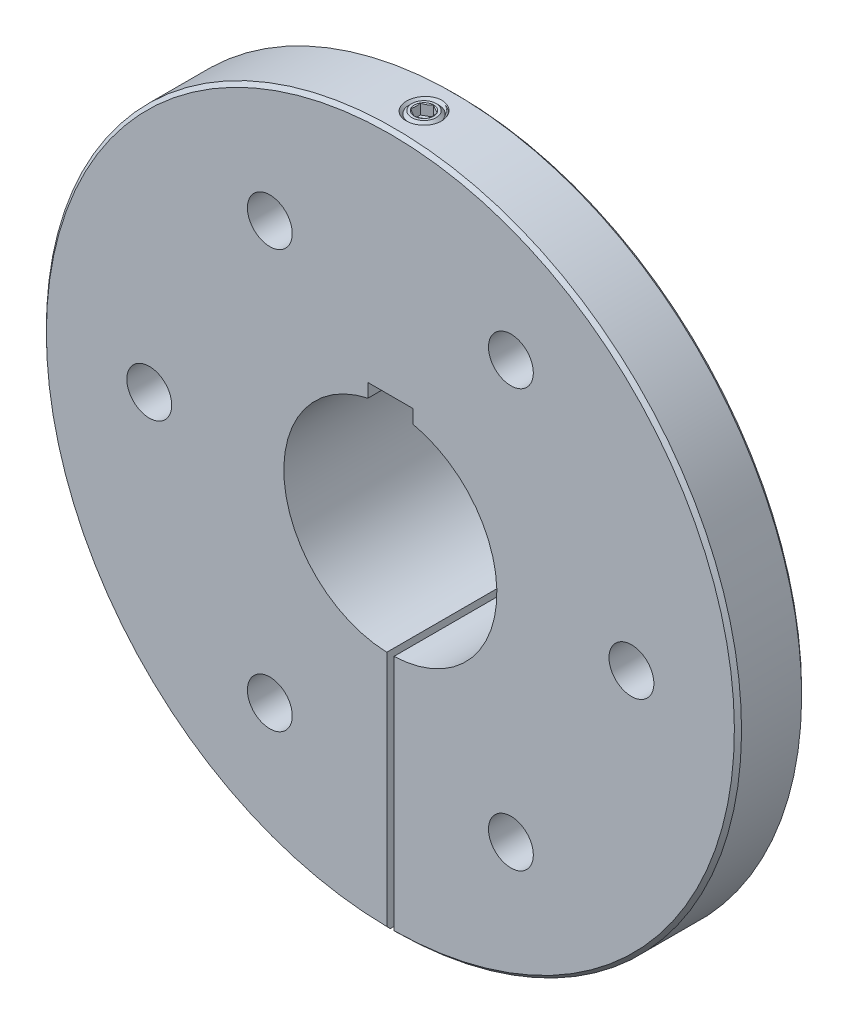
SolidWorks part; units mm, degrees
ref_plane "Front Plane" through (0, 0, 0) normal (0, 0, 1) x (1, 0, 0)
ref_plane "Top Plane" through (0, 0, 0) normal (0, 1, 0) x (1, 0, 0)
ref_plane "Right Plane" through (0, 0, 0) normal (1, 0, 0) x (0, 0, -1)
sketch "Sketch1" plane through (0, 0, 0) normal (1, 0, 0) x (0, 0, -1)
  line L0 (0, 0) -> (26.9875, 0) construction
  line L1 (0, 49.2125) -> (0, -49.2125) construction
  line L2 (12.7, 17.4625) -> (12.7, -17.4625) construction
  line L3 (9.525, 49.2125) -> (9.525, -49.2125) construction
  line L4 (12.7, 17.4625) -> (26.9875, 17.016) construction
  line L5 (26.9875, 17.016) -> (26.9875, -17.016) construction
  line L6 (26.9875, -17.016) -> (12.7, -17.4625)
  line L7 (26.9875, 17.016) -> (26.9875, 49.2125) construction
  line L8 (26.9875, 49.2125) -> (12.7, 49.2125) construction
  line L9 (12.7, 49.2125) -> (12.7, 17.4625) construction
  line L10 (0, 49.2125) -> (9.525, 49.2125) construction
  line L11 (9.525, 49.2125) -> (12.7, 49.2125) construction
  line L12 (0, -49.2125) -> (9.525, -49.2125) construction
  line L13 (26.9875, 0) -> (26.9875, -17.016) construction
  line L14 (26.9875, -15.0812) -> (0, -15.0813)
  line L15 (26.9875, -15.0812) -> (26.9875, -17.016)
  line L16 (0, -15.0813) -> (0, -48.7045)
  line L17 (12.7, -17.4625) -> (12.7, -16.6687)
  line L18 (12.7, -16.6687) -> (9.525, -16.6687)
  line L19 (9.525, -16.6687) -> (9.525, -48.7045)
  line L20 (0, -48.7045) -> (0.508, -49.2125)
  line L21 (0.508, -49.2125) -> (9.017, -49.2125)
  line L22 (9.017, -49.2125) -> (9.525, -48.7045)
  line L23 (26.9875, 17.4625) -> (26.9875, -17.4625) construction
  point P10 (9.525, 0)
  point P11 (12.7, 0)
  dimension "A" = 9.525
  dimension "B" = 34.925
  dimension "D" = 98.425
  dimension "E" = 17.4625
  dimension "F" = 14.2875
  dimension "G" = 3.175
  dimension "L" = 26.9875
  dimension "D2" = 3.175
  dimension "D3" = 0.7937
  dimension "D4" = 0.508
  dimension "Bore" = 30.1625
  dimension "D5" = 45
  dimension "D6" = 0.508
  dimension "D7" = 45
  dimension "Run" = 14.2875
  dimension "Rise" = 0.4465
revolve "Revolve1" add sketch "Sketch1" angle 360 mid plane about L0
sketch "Sketch2" plane through (0, 0, 0) normal (0, 0, 1) x (1, 0, 0)
  circle A0 centre (0, 0) radius 21.1455
  circle A1 centre (0, 0) radius 15.0813
  dimension "Bolt Circle" = 42.291
sketch "Sketch3" plane through (0, 0, 0) normal (0, 0, 1) x (1, 0, 0)
  line L1 (-0.508, 0) -> (0.508, 0)
  line L2 (-0.508, 0) -> (-0.508, -49.2125)
  line L3 (-0.508, -49.2125) -> (0.508, -49.2125)
  line L4 (0.508, 0) -> (0.508, -49.2125)
  dimension "D1" = 1.016
extrude "Cut-Extrude1" cut sketch "Sketch3" against normal through all
sketch "Sketch4" plane through (0, 0, 0) normal (0, 0, 1) x (1, 0, 0)
  line L0 (0, 0) -> (21.1455, 0) construction
  line L1 (0, 0) -> (-21.1455, 0) construction
  circle A0 centre (21.1455, 0) radius 2.413
  circle A1 centre (0, 0) radius 21.1455 construction
  circle A2 centre (-21.1455, 0) radius 2.413
  dimension "D1" = 42.291
  dimension "Cap Screw Size" = 4.826
sketch "Sketch16" plane through (0, 0, 0) normal (0, 0, 1) x (1, 0, 0)
  line L0 (0, 0) -> (0, 13.4938) construction
  line L1 (-3.175, 16.6687) -> (3.175, 16.6687)
  line L2 (-3.175, 16.6687) -> (-3.175, 13.4938)
  line L3 (-3.175, 13.4938) -> (3.175, 13.4938)
  line L4 (3.175, 16.6687) -> (3.175, 13.4938)
  line L5 (-3.175, 15.0813) -> (3.175, 15.0813) construction
  arc A0 (0.508, -15.0727) -> (-0.508, -15.0727) centre (0, 0) ccw construction
  dimension "Key Wd." = 6.35
  dimension "Key Dp." = 1.5875
extrude "Cut-Extrude7" cut sketch "Sketch16" against normal through all
ref_plane "Plane1" through (0, 49.2125, 0) normal (0, 1, 0) x (-1, 0, 0)
sketch "Sketch17" plane through (0, 49.2125, 0) normal (0, 1, 0) x (-1, 0, 0)
  line L0 (0, 0) -> (0, -9.525) construction
  line L1 (-3.175, 0) -> (3.175, 0) construction
  line L2 (-48.7045, -9.525) -> (48.7045, -9.525) construction
  circle A2 centre (0, -4.7625) radius 2.413
  point P1 (0, -2.3495)
  dimension "Set Screw Size" = 4.826
curve "Helix/Spiral3" pitch 1.0583 height 49.2125 turns 46.5 parameters "Pitch"=1.0583
sketch "Sketch18" plane through (0, 0, 0) normal (1, 0, 0) x (0, 0, -1)
  line L0 (3.1515, 50.2708) -> (3.1515, 49.2125) construction
  line L1 (3.1515, 49.2125) -> (2.2349, 49.7417) construction
  line L2 (2.2349, 49.7417) -> (3.1515, 50.2708) construction
  line L3 (2.3495, 49.6755) -> (2.3495, 49.8078) construction
  line L4 (3.0369, 49.2786) -> (3.0369, 50.2047) construction
  line L5 (2.2349, 49.7417) -> (2.3495, 49.7417) construction
  line L6 (3.0369, 49.7417) -> (3.1515, 49.7417) construction
  line L7 (3.0942, 50.2378) -> (3.0942, 49.2456)
  line L8 (3.0942, 49.2456) -> (2.3495, 49.6755)
  line L9 (2.3495, 49.6755) -> (2.3495, 49.8078)
  line L10 (2.3495, 49.8078) -> (3.0942, 50.2378)
  line L12 (2.3495, 49.2125) -> (2.3495, 49.6755) construction
  line L13 (3.1515, 49.2125) -> (2.3495, 49.2125) construction
  point P16 (3.0942, 49.7417)
  dimension "D1" = 1.0583
  dimension "D2" = 0.1323
sketch "Sketch19" plane through (0, 49.2125, 0) normal (0, 1, 0) x (-1, 0, 0)
  circle A0 centre (0, -4.7625) radius 1.7256
extrude "Cut-Extrude9" cut sketch "Sketch19" against normal up to surface (49.2125 mm away) up to plane "Top Plane"
sweep "Cut-Sweep2" cut profiles "Sketch18" path "Helix/Spiral3"
sketch "Sketch20" plane through (0, 49.2125, 0) normal (0, 1, 0) x (-1, 0, 0)
  circle A0 centre (0, -4.7625) radius 2.5276
extrude "Cut-Extrude10" cut sketch "Sketch20" against normal blind 3.175 draft 45
sketch "Sketch21" plane through (0, 0, 0) normal (1, 0, 0) x (0, 0, -1)
  line L0 (4.7625, 16.6688) -> (4.7625, 49.2125) construction
  line L1 (3.0369, 49.2125) -> (4.7625, 49.2125)
  line L2 (2.3495, 48.5251) -> (2.3495, 17.3562)
  line L3 (3.0369, 16.6688) -> (4.7625, 16.6688)
  line L4 (4.7625, 49.2125) -> (4.7625, 16.6688)
  line L6 (3.0369, 49.2786) -> (3.0369, 50.2047) construction
  line L10 (3.0369, 49.2125) -> (2.3495, 48.5251)
  line L11 (2.3495, 17.3562) -> (3.0369, 16.6688)
  line L12 (2.3495, 48.5251) -> (2.3495, 49.2125) construction
  line L13 (2.3495, 49.2125) -> (3.0369, 49.2125) construction
  dimension "D1" = 32.5437
revolve "Revolve2" add sketch "Sketch21" angle 360 mid plane about L0
sketch "Sketch22" plane through (0, 49.2125, 0) normal (0, 1, 0) x (1, 0, 0)
  line L1 (0, 6.1373) -> (-1.1906, 5.4499)
  line L2 (-1.1906, 5.4499) -> (-1.1906, 4.0751)
  line L3 (-1.1906, 4.0751) -> (0, 3.3877)
  line L4 (0, 3.3877) -> (1.1906, 4.0751)
  line L5 (1.1906, 4.0751) -> (1.1906, 5.4499)
  line L6 (1.1906, 5.4499) -> (0, 6.1373)
  circle A0 centre (0, 4.7625) radius 1.1906 construction
  circle A1 centre (0, 4.7625) radius 1.7256 construction
  dimension "Set Screw Hex" = 2.3813
extrude "Cut-Extrude11" cut sketch "Sketch22" against normal blind 1.4883
sketch "Sketch23" plane through (0, 49.2125, 0) normal (0, 1, 0) x (1, 0, 0)
  circle A0 centre (0, 4.7625) radius 1.3748
extrude "Cut-Extrude12" cut sketch "Sketch23" against normal up to vertex (1.4883 mm away) draft 60 up to point (0, 47.7242, -6.1373)
sketch "Sketch24" plane through (0, 0, 0) normal (0, 0, 1) x (1, 0, 0)
  circle A0 centre (-34.1313, 0) radius 3.175
  dimension "D1" = 6.35
  dimension "D2" = 34.1313
extrude "Cut-Extrude13" cut sketch "Sketch24" against normal through all
pattern_circular "CirPattern1" count 6 over 360 about axis through (0, 0, 0) along (0, 0, 1) of "Cut-Extrude13"
